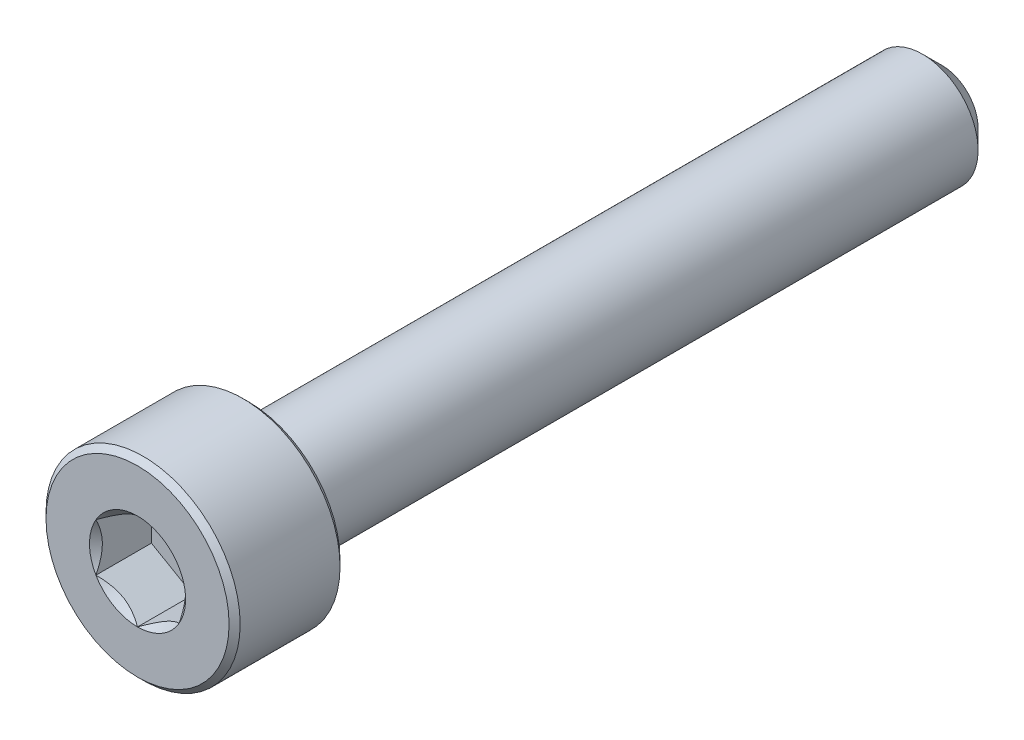
SolidWorks part; units mm, degrees
ref_plane "Front Plane" through (0, 0, 0) normal (0, 0, 1) x (1, 0, 0)
ref_plane "Top Plane" through (0, 0, 0) normal (0, 1, 0) x (1, 0, 0)
ref_plane "Right Plane" through (0, 0, 0) normal (1, 0, 0) x (0, 0, -1)
sketch "Sketch1" plane through (0, 0, 0) normal (1, 0, 0) x (0, 0, -1)
  line L0 (-14.5, 0) -> (14.5, 0) construction
  line L1 (14.5, 0) -> (14.5, 1.3) construction
  line L2 (14.5, 1.3) -> (13.8, 2) construction
  line L3 (13.8, 2) -> (-10.5, 2) construction
  line L5 (-10.5, 2) -> (-10.5, 3.5) construction
  line L6 (-10.5, 3.5) -> (-14.5, 3.5) construction
  line L7 (-14.5, 3.5) -> (-14.5, 0) construction
  line L8 (14.5, 1.3) -> (14.5, 2) construction
  line L9 (14.4563, 2.0758) -> (14.8063, 1.4696) construction
  line L10 (14.8063, 1.4696) -> (15.1563, 2.0758) construction
  line L11 (15.1563, 2.0758) -> (14.4563, 2.0758) construction
  line L12 (14.8063, 2.0758) -> (14.8063, 2) construction
  line L13 (14.8063, 1.4696) -> (14.8063, 1.5453) construction
  line L14 (14.7625, 1.5453) -> (14.85, 1.5453) construction
  line L15 (14.5, 2) -> (15.1125, 2) construction
  line L16 (14.4781, 2.0379) -> (15.1344, 2.0379) construction
  line L17 (14.5, 0) -> (14.5, -2) construction
  line L18 (-10.7, 3.5) -> (-10.5, 3.3) construction
  line L19 (-14.3, 3.5) -> (-14.5, 3.3) construction
  point P0 (-14.5, 1.5)
  point P3 (12.05, 2)
  point P4 (0, 0)
  point P22 (14.8063, 1.5453)
  point P24 (-10.5, 2)
  point P25 (14.8063, 2)
  point P28 (14.8063, 2.0379)
  point P29 (12.05, -2)
  point P31 (-12.5, 3.5)
  point P37 (-11.2, 3.5)
  point P38 (-14.2, 3.5)
  point P41 (-12.5, 0)
  dimension "head height" = 4
  dimension "D1" = 45
  dimension "Head Diameter" = 7
  dimension "Thread Size" = 4
  dimension "drive size" = 3
  dimension "Thread Pitch" = 0.7
  dimension "D2" = 0.0875
  dimension "D3" = 0.7
  dimension "D4" = 2.45
  dimension "D7" = 0.2
  dimension "D8" = 0.2
  dimension "D9" = 0.2
  dimension "D10" = 0.1
  dimension "D11" = 0.5
  dimension "length" = 25
  dimension "Drive Depth" = 2
sketch "Sketch2" plane through (0, 0, 0) normal (1, 0, 0) x (0, 0, -1)
  line L1 (-14.3, 3.5) -> (-10.7, 3.5)
  line L4 (13.8, 2) -> (14.5, 1.3)
  line L5 (14.5, 1.3) -> (14.5, 0)
  line L6 (-10.7, 3.5) -> (-10.5, 3.3) construction
  line L7 (14.5, 0) -> (-14.5, 0)
  line L8 (-14.3, 3.5) -> (-14.5, 3.3) construction
  line L9 (-10.7, 3.5) -> (-10.5, 3.3)
  line L10 (-14.3, 3.5) -> (-14.5, 3.3)
  line L11 (-14.5, 3.3) -> (-14.5, 0)
  line L12 (-10.5, 3.3) -> (-10.5, 2)
  line L13 (-10.5, 2) -> (13.8, 2)
revolve "Revolve1" add sketch "Sketch2" angle 360 about L7
sketch "Sketch3" plane through (0, 0, 14.5) normal (0, 0, 1) x (1, 0, 0)
  line L1 (0, 1.7321) -> (-1.5, 0.866)
  line L2 (-1.5, 0.866) -> (-1.5, -0.866)
  line L3 (-1.5, -0.866) -> (0, -1.7321)
  line L4 (0, -1.7321) -> (1.5, -0.866)
  line L5 (1.5, -0.866) -> (1.5, 0.866)
  line L6 (1.5, 0.866) -> (0, 1.7321)
  circle A0 centre (0, 0) radius 1.5 construction
  dimension "D1" = 3
extrude "Cut-Extrude1" cut sketch "Sketch3" against normal up to vertex (2 mm away) up to point (0, 0, 12.5)
sketch "Sketch4" plane through (0, 0, 14.5) normal (0, 0, 1) x (1, 0, 0)
  circle A0 centre (0, 0) radius 1.7321
extrude "Cut-Extrude2" cut sketch "Sketch4" against normal blind 0.5 draft 45
ref_plane "Plane1" [suppressed] through (0, 0, 10.5) normal (0, 0, 1) x (1, 0, 0)
split "Split1" [suppressed] bodies to split 106
sketch "Sketch6" [suppressed] plane through (0, 0, -14.5) normal (0, 0, -1) x (-1, 0, 0)
  circle A0 centre (0, 0) radius 2
curve "Helix/Spiral1" [suppressed] pitch 0.7 height 25.7 turns 36.7143
sketch "Sketch7" [suppressed] plane through (0, 0, 0) normal (1, 0, 0) x (0, 0, -1)
  line L0 (14.4781, 2.0379) -> (15.1344, 2.0379)
  line L1 (15.1344, 2.0379) -> (14.85, 1.5453)
  line L2 (14.85, 1.5453) -> (14.7625, 1.5453)
  line L3 (14.7625, 1.5453) -> (14.4781, 2.0379)
sweep "Cut-Sweep1" [suppressed] cut profiles "Sketch7" path "Helix/Spiral1"
sketch "Sketch8" [suppressed] plane through (0, 0, 10.5) normal (0, 0, -1) x (-1, 0, 0)
  circle A0 centre (0, 0) radius 2
extrude "Boss-Extrude1" [suppressed] add sketch "Sketch8" along normal through all draft 45
ref_plane "Plane2" [suppressed] through (0, 0, 12.5) normal (0, 0, 1) x (1, 0, 0)
sketch "Sketch9" [suppressed] plane through (0, 0, 12.5) normal (0, 0, 1) x (1, 0, 0)
  line L0 (0, 3.4038) -> (0.0916, 3.4988)
  line L1 (0, 3.4038) -> (-0.0916, 3.4988)
  line L2 (0, 3.5) -> (0, 0) construction
  line L3 (-0.0916, 3.4988) -> (0, 0) construction
  line L4 (0, 0) -> (0.0916, 3.4988) construction
  arc A0 (0.0916, 3.4988) -> (-0.0916, 3.4988) centre (0, 0) ccw
  circle A1 centre (0, 0) radius 3.4038 construction
  dimension "D1" = 7
  dimension "D2" = 6.8075
  dimension "D3" = 3
extrude "Cut-Extrude4" [suppressed] cut sketch "Sketch9" against normal up to vertex and the other way up to vertex
pattern_circular "CirPattern2" [suppressed] count 96 over 360 about axis through (0, 0, 14.5) along (0, 0, -1) of bodies 113
equation "\"D2@Sketch1\" = \"Thread Pitch@Sketch1\" / 8"
equation "\"D3@Sketch1\" = \"Thread Pitch@Sketch1\""
equation "\"D3@Helix/Spiral1\" = \"length@Sketch1\" + \"Thread Pitch@Sketch1\""
equation "\"D4@Helix/Spiral1\" = \"Thread Pitch@Sketch1\""
equation "\"D4@Sketch1\" = \"Thread Pitch@Sketch1\" * 3.5"
equation "\"D7@Sketch1\"=\"head height@Sketch1\"*.05"
equation "\"D8@Sketch1\"=\"D7@Sketch1\""
equation "\"D9@Sketch1\"=\"D7@Sketch1\""
equation "\"D10@Sketch1\"=\"D7@Sketch1\"/2"
equation "\"D11@Sketch1\"=\"D10@Sketch1\"*5"
equation "\"D1@CirPattern2\"=( 360 / \"D3@Sketch9\" )*0.8"
equation "\"D1@Sketch3\" = \"drive size@Sketch1\""
equation "\"D2@Sketch9\"=\"Head Diameter@Sketch1\" * 0.9725"
